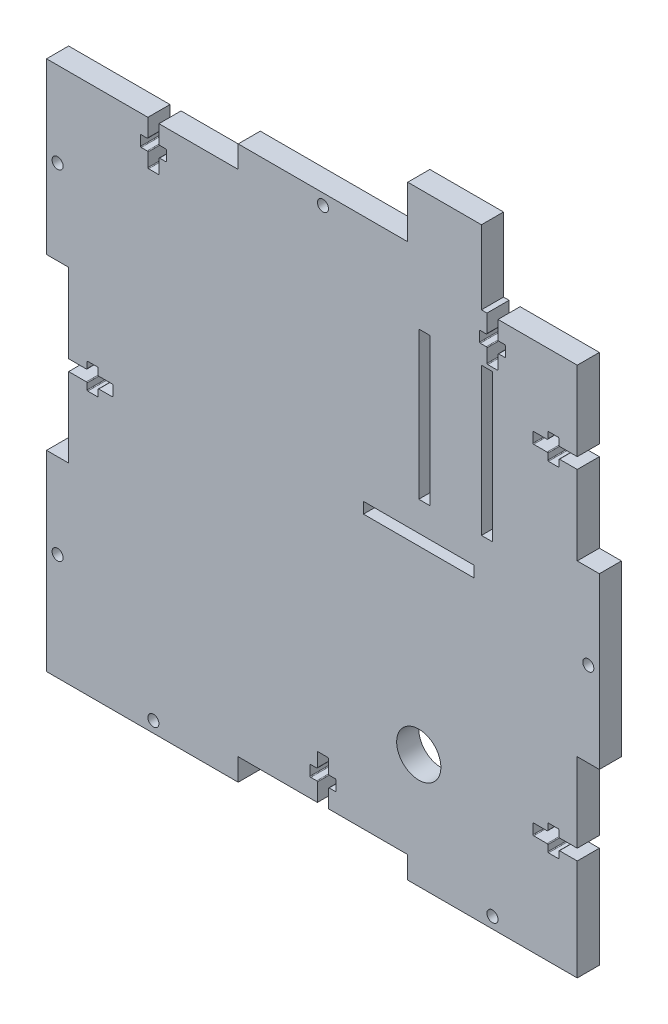
SolidWorks part; units mm, degrees
ref_plane "Front Plane" through (0, 0, 0) normal (0, 0, 1) x (1, 0, 0)
ref_plane "Top Plane" through (0, 0, 0) normal (0, 1, 0) x (1, 0, 0)
ref_plane "Right Plane" through (0, 0, 0) normal (1, 0, 0) x (0, 0, -1)
sketch "Sketch1" plane through (0, 0, 0) normal (0, 0, 1) x (1, 0, 0)
  line L0 (-69, 69) -> (-23, 69)
  line L5 (-75, -75) -> (75, -75) construction
  line L6 (-75, -75) -> (-75, 75) construction
  line L7 (-75, 75) -> (75, 75) construction
  line L8 (75, -75) -> (75, 75) construction
  line L9 (75, 23) -> (69, 23)
  line L10 (69, -23) -> (75, -23)
  line L11 (-69, -69) -> (69, -69) construction
  line L12 (-69, -69) -> (-69, 69) construction
  line L13 (-69, 69) -> (69, 69) construction
  line L14 (69, -69) -> (69, 69) construction
  line L15 (-69, -69) -> (69, 69) construction
  line L16 (69, -69) -> (69, -23)
  line L17 (-23, 69) -> (-23, 75)
  line L18 (-23, 75) -> (23, 75)
  line L19 (23, 75) -> (23, 69)
  line L20 (23, 69) -> (69, 69)
  line L21 (75, -23) -> (75, 23)
  line L22 (69, 23) -> (69, 69)
  line L23 (-75, 23) -> (-69, 23)
  line L24 (-69, 69) -> (-75, 69)
  line L25 (-75, 69) -> (-75, 23)
  line L26 (69, -69) -> (69, -75)
  line L27 (69, -75) -> (23, -75)
  line L28 (23, -75) -> (23, -69)
  line L29 (23, -69) -> (-23, -69)
  line L30 (-23, -69) -> (-23, -75)
  line L31 (-23, -75) -> (-69, -75)
  line L32 (-69, -75) -> (-69, -69) construction
  line L33 (-69, 23) -> (-69, -23)
  line L34 (-69, -23) -> (-75, -23)
  line L35 (-75, -23) -> (-75, -69)
  line L36 (-75, -69) -> (-69, -69) construction
  line L37 (-46, 69) -> (-46, -75) construction
  line L38 (-69, 69) -> (69, -69) construction
  line L39 (-75, -75) -> (-69, -75)
  line L40 (-75, -75) -> (-75, -69)
  point P0 (0, 0)
  point P6 (-7, -7)
  point P26 (0, -75)
  point P27 (-75, 0)
  dimension "D1" = 150
  dimension "D2" = 150
  dimension "D5" = 46
  dimension "D3" = 6
  dimension "D6" = 6
  dimension "D7" = 6
extrude "Box Side" add sketch "Sketch1" along normal blind 6
sketch "Sketch2" plane through (0, 0, 6) normal (0, 0, 1) x (1, 0, 0)
  line L0 (23, 72) -> (-23, 72) construction
  line L1 (23, 75) -> (23, 69) construction
  line L2 (-23, 69) -> (-23, 75) construction
  line L3 (-46, 69) -> (-46, -75) construction
  line L5 (0, 75) -> (0, 69) construction
  line L6 (-23, 75) -> (23, 75) construction
  line L7 (-69, 69) -> (69, 69) construction
  line L16 (-46, 69) -> (-46, -75) construction
  line L21 (0, -69) -> (0, 69) construction
  line L35 (-69, 69) -> (-23, 69) construction
  line L36 (-44.5, 69) -> (-44.5, 64.2)
  line L37 (-44.3, 64) -> (-42.7, 64)
  line L38 (-42.5, 63.8) -> (-42.5, 61.2)
  line L39 (-42.7, 61) -> (-44.3, 61)
  line L40 (-44.5, 60.8) -> (-44.5, 57.2)
  line L46 (-44.7, 57) -> (-47.3, 57)
  line L48 (-44.5, 69) -> (-47.5, 69)
  line L51 (-47.5, 60.8) -> (-47.5, 57.2)
  line L52 (-49.3, 61) -> (-47.7, 61)
  line L53 (-49.5, 63.8) -> (-49.5, 61.2)
  line L54 (-47.7, 64) -> (-49.3, 64)
  line L55 (-47.5, 69) -> (-47.5, 64.2)
  line L56 (47.5, 69) -> (47.5, 64.2)
  line L57 (47.7, 64) -> (49.3, 64)
  line L58 (49.5, 63.8) -> (49.5, 61.2)
  line L59 (49.3, 61) -> (47.7, 61)
  line L60 (47.5, 60.8) -> (47.5, 57.2)
  line L61 (44.5, 69) -> (47.5, 69)
  line L62 (44.7, 57) -> (47.3, 57)
  line L63 (44.5, 60.8) -> (44.5, 57.2)
  line L64 (42.7, 61) -> (44.3, 61)
  line L65 (42.5, 63.8) -> (42.5, 61.2)
  line L66 (44.3, 64) -> (42.7, 64)
  line L67 (44.5, 69) -> (44.5, 64.2)
  line L68 (-69, -69) -> (69, 69) construction
  line L69 (-69, -69) -> (69, 69) construction
  line L70 (75, 0) -> (69, 0) construction
  line L71 (72, 23) -> (72, -23) construction
  line L72 (69, 44.5) -> (64.2, 44.5)
  line L73 (64, 44.3) -> (64, 42.7)
  line L74 (63.8, 42.5) -> (61.2, 42.5)
  line L75 (61, 42.7) -> (61, 44.3)
  line L76 (60.8, 44.5) -> (57.2, 44.5)
  line L77 (57, 44.7) -> (57, 47.3)
  line L78 (69, 44.5) -> (69, 47.5)
  line L79 (60.8, 47.5) -> (57.2, 47.5)
  line L80 (61, 49.3) -> (61, 47.7)
  line L81 (63.8, 49.5) -> (61.2, 49.5)
  line L82 (64, 47.7) -> (64, 49.3)
  line L83 (69, 47.5) -> (64.2, 47.5)
  line L84 (69, -47.5) -> (64.2, -47.5)
  line L85 (64, -47.7) -> (64, -49.3)
  line L86 (63.8, -49.5) -> (61.2, -49.5)
  line L87 (61, -49.3) -> (61, -47.7)
  line L88 (60.8, -47.5) -> (57.2, -47.5)
  line L89 (69, -44.5) -> (69, -47.5)
  line L90 (57, -44.7) -> (57, -47.3)
  line L91 (60.8, -44.5) -> (57.2, -44.5)
  line L92 (61, -42.7) -> (61, -44.3)
  line L93 (63.8, -42.5) -> (61.2, -42.5)
  line L94 (64, -44.3) -> (64, -42.7)
  line L95 (69, -44.5) -> (64.2, -44.5)
  line L120 (-69, 69) -> (69, -69) construction
  line L121 (-69, 69) -> (69, -69) construction
  line L122 (-1.5, -69) -> (1.5, -69)
  line L123 (-23, -69) -> (23, -69) construction
  line L124 (1.5, -69) -> (1.5, -64.2)
  line L125 (1.7, -64) -> (3.3, -64)
  line L126 (3.5, -63.8) -> (3.5, -61.2)
  line L127 (3.3, -61) -> (1.7, -61)
  line L128 (1.5, -60.8) -> (1.5, -57.2)
  line L129 (1.3, -57) -> (-1.3, -57)
  line L130 (-1.5, -60.8) -> (-1.5, -57.2)
  line L131 (-3.3, -61) -> (-1.7, -61)
  line L132 (-3.5, -63.8) -> (-3.5, -61.2)
  line L133 (-1.7, -64) -> (-3.3, -64)
  line L134 (-1.5, -69) -> (-1.5, -64.2)
  line L135 (-69, -1.5) -> (-64.2, -1.5)
  line L136 (-64, -1.7) -> (-64, -3.3)
  line L137 (-63.8, -3.5) -> (-61.2, -3.5)
  line L138 (-61, -3.3) -> (-61, -1.7)
  line L139 (-60.8, -1.5) -> (-57.2, -1.5)
  line L140 (-57, 1.3) -> (-57, -1.3)
  line L141 (-60.8, 1.5) -> (-57.2, 1.5)
  line L142 (-61, 3.3) -> (-61, 1.7)
  line L143 (-63.8, 3.5) -> (-61.2, 3.5)
  line L144 (-64, 1.7) -> (-64, 3.3)
  line L145 (-69, 1.5) -> (-64.2, 1.5)
  line L146 (-69, -1.5) -> (-69, 1.5)
  line L147 (-69, -72) -> (-23, -72) construction
  line L148 (-23, 69) -> (-75, 69) construction
  line L149 (-23, -75) -> (-23, -69) construction
  line L150 (-69, -69) -> (-69, -75) construction
  line L151 (-75, -75) -> (-23, -75) construction
  circle A0 centre (0, 72) radius 1.5
  arc A1 (-44.5, 57.2) -> (-44.7, 57) centre (-44.7, 57.2) cw
  arc A2 (-44.3, 61) -> (-44.5, 60.8) centre (-44.3, 60.8) ccw
  arc A3 (-42.5, 61.2) -> (-42.7, 61) centre (-42.7, 61.2) cw
  arc A4 (-42.7, 64) -> (-42.5, 63.8) centre (-42.7, 63.8) cw
  arc A5 (-44.5, 64.2) -> (-44.3, 64) centre (-44.3, 64.2) ccw
  arc A6 (-47.5, 64.2) -> (-47.7, 64) centre (-47.7, 64.2) cw
  arc A7 (-49.3, 64) -> (-49.5, 63.8) centre (-49.3, 63.8) ccw
  arc A8 (-49.5, 61.2) -> (-49.3, 61) centre (-49.3, 61.2) ccw
  arc A9 (-47.7, 61) -> (-47.5, 60.8) centre (-47.7, 60.8) cw
  arc A10 (-47.5, 57.2) -> (-47.3, 57) centre (-47.3, 57.2) ccw
  arc A11 (47.5, 57.2) -> (47.3, 57) centre (47.3, 57.2) cw
  arc A12 (47.7, 61) -> (47.5, 60.8) centre (47.7, 60.8) ccw
  arc A13 (49.5, 61.2) -> (49.3, 61) centre (49.3, 61.2) cw
  arc A14 (49.3, 64) -> (49.5, 63.8) centre (49.3, 63.8) cw
  arc A15 (47.5, 64.2) -> (47.7, 64) centre (47.7, 64.2) ccw
  arc A16 (44.5, 64.2) -> (44.3, 64) centre (44.3, 64.2) cw
  arc A17 (42.7, 64) -> (42.5, 63.8) centre (42.7, 63.8) ccw
  arc A18 (42.5, 61.2) -> (42.7, 61) centre (42.7, 61.2) ccw
  arc A19 (44.3, 61) -> (44.5, 60.8) centre (44.3, 60.8) cw
  arc A20 (44.5, 57.2) -> (44.7, 57) centre (44.7, 57.2) ccw
  arc A21 (57.2, 44.5) -> (57, 44.7) centre (57.2, 44.7) cw
  arc A22 (61, 44.3) -> (60.8, 44.5) centre (60.8, 44.3) ccw
  arc A23 (61.2, 42.5) -> (61, 42.7) centre (61.2, 42.7) cw
  arc A24 (64, 42.7) -> (63.8, 42.5) centre (63.8, 42.7) cw
  arc A25 (64.2, 44.5) -> (64, 44.3) centre (64.2, 44.3) ccw
  arc A26 (64.2, 47.5) -> (64, 47.7) centre (64.2, 47.7) cw
  arc A27 (64, 49.3) -> (63.8, 49.5) centre (63.8, 49.3) ccw
  arc A28 (61.2, 49.5) -> (61, 49.3) centre (61.2, 49.3) ccw
  arc A29 (61, 47.7) -> (60.8, 47.5) centre (60.8, 47.7) cw
  arc A30 (57.2, 47.5) -> (57, 47.3) centre (57.2, 47.3) ccw
  arc A31 (57.2, -47.5) -> (57, -47.3) centre (57.2, -47.3) cw
  arc A32 (61, -47.7) -> (60.8, -47.5) centre (60.8, -47.7) ccw
  arc A33 (61.2, -49.5) -> (61, -49.3) centre (61.2, -49.3) cw
  arc A34 (64, -49.3) -> (63.8, -49.5) centre (63.8, -49.3) cw
  arc A35 (64.2, -47.5) -> (64, -47.7) centre (64.2, -47.7) ccw
  arc A36 (64.2, -44.5) -> (64, -44.3) centre (64.2, -44.3) cw
  arc A37 (64, -42.7) -> (63.8, -42.5) centre (63.8, -42.7) ccw
  arc A38 (61.2, -42.5) -> (61, -42.7) centre (61.2, -42.7) ccw
  arc A39 (61, -44.3) -> (60.8, -44.5) centre (60.8, -44.3) cw
  arc A40 (57.2, -44.5) -> (57, -44.7) centre (57.2, -44.7) ccw
  circle A41 centre (72, 0) radius 1.5
  arc A62 (1.5, -57.2) -> (1.3, -57) centre (1.3, -57.2) ccw
  arc A63 (1.7, -61) -> (1.5, -60.8) centre (1.7, -60.8) cw
  arc A64 (3.5, -61.2) -> (3.3, -61) centre (3.3, -61.2) ccw
  arc A65 (3.3, -64) -> (3.5, -63.8) centre (3.3, -63.8) ccw
  arc A66 (1.5, -64.2) -> (1.7, -64) centre (1.7, -64.2) cw
  arc A67 (-1.5, -64.2) -> (-1.7, -64) centre (-1.7, -64.2) ccw
  arc A68 (-3.3, -64) -> (-3.5, -63.8) centre (-3.3, -63.8) cw
  arc A69 (-3.5, -61.2) -> (-3.3, -61) centre (-3.3, -61.2) cw
  arc A70 (-1.7, -61) -> (-1.5, -60.8) centre (-1.7, -60.8) ccw
  arc A71 (-1.5, -57.2) -> (-1.3, -57) centre (-1.3, -57.2) cw
  arc A72 (-57.2, -1.5) -> (-57, -1.3) centre (-57.2, -1.3) ccw
  arc A73 (-61, -1.7) -> (-60.8, -1.5) centre (-60.8, -1.7) cw
  arc A74 (-61.2, -3.5) -> (-61, -3.3) centre (-61.2, -3.3) ccw
  arc A75 (-64, -3.3) -> (-63.8, -3.5) centre (-63.8, -3.3) ccw
  arc A76 (-64.2, -1.5) -> (-64, -1.7) centre (-64.2, -1.7) cw
  arc A77 (-64.2, 1.5) -> (-64, 1.7) centre (-64.2, 1.7) ccw
  arc A78 (-64, 3.3) -> (-63.8, 3.5) centre (-63.8, 3.3) cw
  arc A79 (-61.2, 3.5) -> (-61, 3.3) centre (-61.2, 3.3) cw
  arc A80 (-61, 1.7) -> (-60.8, 1.5) centre (-60.8, 1.7) ccw
  arc A81 (-57.2, 1.5) -> (-57, 1.3) centre (-57.2, 1.3) cw
  circle A82 centre (-46, -72) radius 1.5
  circle A83 centre (46, -72) radius 1.5
  circle A84 centre (-72, 46) radius 1.5
  circle A85 centre (-72, -46) radius 1.5
  point P6 (0, 72)
  point P38 (0, 0)
  point P56 (-46, 57)
  point P88 (46, 57)
  point P161 (57, 46)
  point P162 (57, -46)
  point P198 (0, -57)
  point P231 (-57, 0)
  point P234 (-42.5, 62.5)
  dimension "D1" = 3
  dimension "D2" = 0.2
  dimension "D8" = 0.2
  dimension "D14" = 3
  dimension "D4" = 3
  dimension "D7" = 1.5
  dimension "D10" = 3
  dimension "D12" = 1.5
  dimension "D9" = 12
  dimension "D11" = 5
  dimension "D13" = 7
  dimension "D3" = 12
  dimension "D5" = 7
  dimension "D6" = 5
extrude "Screw Cut-outs" cut sketch "Sketch2" against normal through all
sketch "Bearing Hole" plane through (0, 0, 6) normal (0, 0, 1) x (1, 0, 0)
  line L0 (20, -69) -> (50020, -69) construction
  line L1 (69, -44.5) -> (69, -23) construction
  line L4 (26, -41) -> (50026, -41) construction
  line L5 (26.5774, -47) -> (50026.5774, -47) construction
  line L8 (29, -52) -> (29, -50052) construction
  circle A0 centre (26, -44) radius 3 construction
  circle A1 centre (26, -54) radius 15 construction
  circle A2 centre (26, -44) radius 6
  dimension "D2" = 6
  dimension "D4" = 30
  dimension "D5" = 12
  dimension "D1" = 7
  dimension "D3" = 43
extrude "Shaft Hole" cut sketch "Bearing Hole" against normal through all
sketch "Sketch4" plane through (0, 0, 0) normal (0, 0, -1) x (-1, 0, 0)
  line L0 (-72, 1.5) -> (49928, 1.5) construction
  line L1 (-41, 8) -> (-11, 8)
  line L2 (-41, 8) -> (-41, 5)
  line L3 (-41, 5) -> (-11, 5)
  line L4 (-11, 8) -> (-11, 5)
  line L5 (-75, -23) -> (-75, 23) construction
  line L6 (-69, 23) -> (-69, 44.5) construction
  line L7 (-46, 56) -> (-43, 56)
  line L8 (-46, 56) -> (-46, 16)
  line L9 (-46, 16) -> (-43, 16)
  line L10 (-43, 56) -> (-43, 16)
  line L11 (-29, 56) -> (-26, 56)
  line L12 (-29, 56) -> (-29, 16)
  line L13 (-29, 16) -> (-26, 16)
  line L14 (-26, 56) -> (-26, 16)
  line L15 (-44.5, 69) -> (-23, 69) construction
  circle A1 centre (-72, 0) radius 1.5 construction
  point P18 (-29, 36)
  dimension "D1" = 3.5
  dimension "D2" = 30
  dimension "D3" = 3
  dimension "D4" = 34
  dimension "D5" = 14
  dimension "D6" = 23
  dimension "D7" = 13
  dimension "D8" = 3
  dimension "D9" = 40
extrude "Grooves" cut sketch "Sketch4" against normal up to surface (6 mm away) up to face at (32, -44, 6)
sketch "Sketch5" plane through (0, 69, 0) normal (0, 1, 0) x (1, 0, 0)
  line L0 (69, 0) -> (47.5, 0) construction
  line L1 (23, -6) -> (43, -6)
  line L2 (23, -6) -> (23, 0)
  line L3 (23, 0) -> (43, 0)
  line L4 (43, -6) -> (43, 0)
  line L5 (75, -6) -> (75, 0) construction
  dimension "D1" = 32
extrude "Boss-Extrude1" add sketch "Sketch5" along normal blind 20
equation "\"filletRadius\"=0.2"
equation "\"D8@Sketch2\"=\"filletRadius\""
equation "\"D2@Sketch2\"=\"filletRadius\""
equation "\"fingerWidth\"= 46"
equation "\"D5@Sketch1\"=\"fingerWidth\""
equation "\"wallThickness\"= 6"
equation "\"D3@Sketch1\" = \"wallThickness\""
equation "\"D6@Sketch1\" = \"wallThickness\""
equation "\"D7@Sketch1\" = \"wallThickness\""
equation "\"D1@Box Side\" = \"wallThickness\""
equation "\"M3\"= 3"
equation "\"D14@Sketch2\"=\"M3\""
equation "\"D1@Sketch2\"=\"M3\""
equation "\"D12@Sketch2\"=\"M3\"/2"
equation "\"nutThickness\"=3"
equation "\"D10@Sketch2\" = \"nutThickness\""
equation "\"boltLength\"= 12"
equation "\"D9@Sketch2\" = \"boltLength\""
equation "\"distanceToNut\"= 5"
equation "\"D11@Sketch2\" = \"distanceToNut\""
equation "\"D13@Sketch2\" = \"nutWidth\""
equation "\"D7@Sketch2\"=\"M3\"/2"
equation "\"D4@Sketch2\" = \"nutThickness\""
equation "\"D3@Sketch2\" = \"boltLength\""
equation "\"D5@Sketch2\" = \"nutWidth\""
equation "\"D6@Sketch2\" = \"distanceToNut\""
equation "\"sideLength\"=150"
equation "\"D1@Sketch1\"=\"sideLength\""
equation "\"D2@Sketch1\"=\"sideLength\""
equation "\"nutWidth\"=7"
